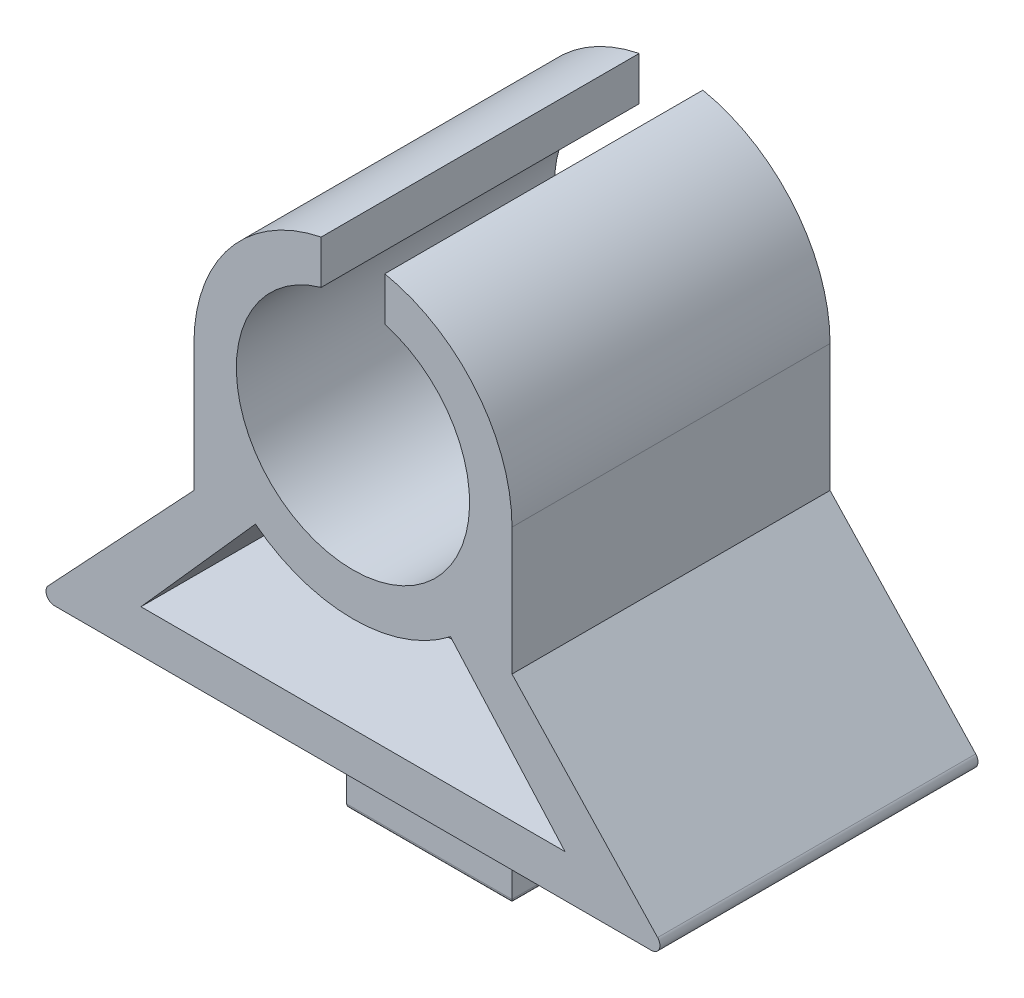
SolidWorks part; units mm, degrees
ref_plane "前视基准面" through (0, 0, 0) normal (0, 0, 1) x (1, 0, 0)
ref_plane "上视基准面" through (0, 0, 0) normal (0, 1, 0) x (1, 0, 0)
ref_plane "右视基准面" through (0, 0, 0) normal (1, 0, 0) x (0, 0, -1)
sketch "草图1" plane through (0, 0, 0) normal (0, 0, 1) x (1, 0, 0)
  line L0 (-7.5, 0) -> (7.5, 0)
  line L2 (-7.5, 0) -> (-3.75, 4)
  line L3 (3.75, 4) -> (7.5, 0)
  line L4 (-3.75, 4) -> (-3.75, 7)
  line L5 (3.75, 4) -> (3.75, 7)
  line L7 (-0.75, 9.6458) -> (-0.75, 10.6742)
  line L9 (0.75, 9.6458) -> (0.75, 10.6742)
  arc A0 (3.75, 7) -> (0.75, 10.6742) centre (0, 7) ccw
  arc A1 (-0.75, 9.6458) -> (0.75, 9.6458) centre (0, 7) ccw
  arc A2 (-0.75, 10.6742) -> (-3.75, 7) centre (0, 7) ccw
extrude "凸台-拉伸1" add sketch "草图1" along normal blind 3.75 and the other way blind 3.75
sketch "草图2" plane through (0, 0, 0) normal (0, -1, 0) x (1, 0, 0)
  line L1 (-1.5, 1.5) -> (1.5, 1.5)
  line L2 (-1.5, 1.5) -> (-1.5, -1.5)
  line L3 (-1.5, -1.5) -> (1.5, -1.5)
  line L4 (1.5, 1.5) -> (1.5, -1.5)
extrude "凸台-拉伸2" add sketch "草图2" along normal blind 1
sketch "草图3" plane through (0, 0, 0) normal (0, 0, 1) x (1, 0, 0)
  line L0 (-1.95, -2.5) -> (1.95, -2.5)
  line L1 (-1.95, -2.5) -> (-1.95, -1.5556)
  line L2 (1.95, -2.5) -> (1.95, -1.5556)
  line L4 (-1.5, -1) -> (-1.5, 0) construction
  line L5 (-1.5, -0.6771) -> (1.5, -0.6771)
  arc A0 (1.95, -1.5556) -> (1.5, -0.6771) centre (0, -2) ccw
  arc A1 (-1.5, -0.6771) -> (-1.95, -1.5556) centre (0, -2) ccw
extrude "凸台-拉伸3" add sketch "草图3" along normal blind 2 and the other way blind 2
sketch "草图4" plane through (-1.95, 0, 0) normal (-1, 0, 0) x (0, 0, 1)
  line L0 (-1.95, -2.5) -> (-1.95, -1.5556)
  line L1 (1.95, -2.5) -> (1.95, -1.5556)
  line L2 (1.95, -2.5) -> (2, -2.5)
  line L3 (-1.95, -0.6771) -> (-1.5, -0.6771)
  line L4 (-1.5, -0.6771) -> (-2, -0.6771)
  line L5 (-2, -0.6771) -> (-2, -2.5)
  line L6 (-2, -2.5) -> (-1.95, -2.5)
  line L7 (2, -2.5) -> (2, -0.6771)
  line L8 (1.5, -0.6771) -> (2, -0.6771)
  arc A0 (1.95, -1.5556) -> (1.5, -0.6771) centre (0, -2) ccw
  arc A1 (-1.5, -0.6771) -> (-1.95, -1.5556) centre (0, -2) ccw
extrude "切除-拉伸1" cut sketch "草图4" against normal up to next contours L4 L5 L6 L0 A1 | L7 L8 A0 L1 L2
sketch "草图5" plane through (0, 0, 3.75) normal (0, 0, 1) x (1, 0, 0)
  line L0 (-5, 1) -> (5, 1)
  line L3 (-5, 1) -> (-2.2997, 4.0379)
  line L4 (2.2997, 4.0379) -> (5, 1)
  arc A0 (-2.2997, 4.0379) -> (2.2997, 4.0379) centre (0, 7) ccw
extrude "切除-拉伸2" cut sketch "草图5" against normal blind 3
extrude "切除-拉伸3" cut sketch "草图5<2>" along normal blind 3 from offset 7.5 offset against normal yes
sketch "草图5<2>" plane through (0, 0, 3.75) normal (0, 0, 1) x (1, 0, 0) same geometry as "草图5"
fillet "圆角1" radius 0.2 2 edges at (-7.5, 0, 0) (7.5, 0, 0)
fillet "圆角2" radius 0.1 4 edges at (0, -2.5, -1.95) (-1.95, -2.5, 0) (0, -2.5, 1.95) (1.95, -2.5, 0)
